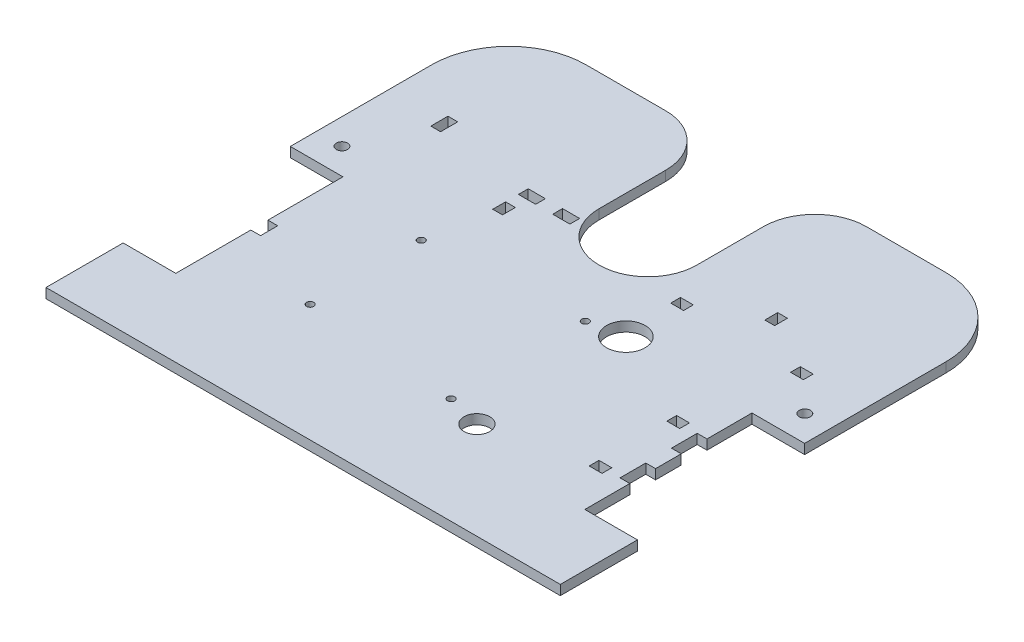
SolidWorks part; units mm, degrees
ref_plane "Front Plane" through (0, 0, 0) normal (0, 0, 1) x (1, 0, 0)
ref_plane "Top Plane" through (0, 0, 0) normal (0, 1, 0) x (1, 0, 0)
ref_plane "Right Plane" through (0, 0, 0) normal (1, 0, 0) x (0, 0, -1)
sketch "Sketch1" plane through (0, 0, 0) normal (0, 1, 0) x (1, 0, 0)
  line L1 (-127, 114.3) -> (127, 114.3)
  line L2 (-127, 114.3) -> (-127, -114.3)
  line L3 (-127, -114.3) -> (127, -114.3)
  line L4 (127, 114.3) -> (127, -114.3)
  line L5 (-127, 114.3) -> (127, -114.3) construction
  line L6 (-127, -114.3) -> (127, 114.3) construction
  point P0 (0, 0)
  dimension "D1" = 254
  dimension "D2" = 228.6
extrude "Boss-Extrude1" add sketch "Sketch1" along normal blind 4.826
sketch "Sketch2" plane through (0, 4.826, 0) normal (0, 1, 0) x (1, 0, 0)
  line L0 (-127, 114.3) -> (-127, -114.3) construction
  line L1 (-127, 6.35) -> (-101, 6.35)
  line L2 (-127, 6.35) -> (-127, -76.2)
  line L3 (-127, -76.2) -> (-101, -76.2)
  line L4 (-101, 6.35) -> (-101, -76.2)
  line L5 (127, -114.3) -> (127, 114.3) construction
  line L6 (127, 6.35) -> (101, 6.35)
  line L7 (127, 6.35) -> (127, -76.2)
  line L8 (127, -76.2) -> (101, -76.2)
  line L9 (101, 6.35) -> (101, -76.2)
  line L10 (-127, -114.3) -> (127, -114.3) construction
  dimension "D1" = 38.1
  dimension "D2" = 38.1
  dimension "D3" = 82.55
  dimension "D4" = 82.55
  dimension "D5" = 26
  dimension "D6" = 26
extrude "Cut-Extrude1" cut sketch "Sketch2" against normal blind 4.826
sketch "Sketch4" plane through (0, 4.826, 0) normal (0, 1, 0) x (1, 0, 0)
  line L0 (0, -114.3) -> (0, 114.3) construction
  line L1 (-127, -114.3) -> (127, -114.3) construction
  line L2 (127, 114.3) -> (-127, 114.3) construction
  line L3 (-127, 76.2) -> (-88.9, 76.2) construction
  line L4 (-127, 114.3) -> (-127, 6.35) construction
  line L5 (-88.9, 76.2) -> (-88.9, 114.3) construction
  line L6 (-127, 76.2) -> (-127, 114.3)
  line L7 (-127, 114.3) -> (-88.9, 114.3)
  line L8 (127, 76.2) -> (127, 114.3)
  line L9 (127, 114.3) -> (88.9, 114.3)
  arc A0 (-127, 76.2) -> (-88.9, 114.3) centre (-88.9, 76.2) cw
  arc A1 (127, 76.2) -> (88.9, 114.3) centre (88.9, 76.2) ccw
  dimension "D1" = 38.1
  dimension "D2" = 38.1
extrude "Cut-Extrude3" cut sketch "Sketch4" against normal blind 4.826
sketch "Sketch17" plane through (0, 0, 0) normal (0, -1, 0) x (1, 0, 0)
  circle A0 centre (114.3, -19.1646) radius 2.7781 construction
  circle A1 centre (-114.3, -19.1646) radius 2.7781 construction
  circle A2 centre (114.3, -19.1646) radius 2.7781
  circle A3 centre (-114.3, -19.1646) radius 2.7781
extrude "Cut-Extrude14" cut sketch "Sketch17" against normal through all
sketch "Sketch18" plane through (0, 4.826, 0) normal (0, 1, 0) x (1, 0, 0)
  line L0 (101, -53.975) -> (96.174, -53.975) construction
  line L1 (96.174, -41.275) -> (96.174, -53.975) construction
  line L2 (101, -41.275) -> (96.174, -41.275) construction
  line L3 (101, -41.275) -> (101, -53.975) construction
  line L4 (101, -15.875) -> (101, -28.575) construction
  line L5 (101, -15.875) -> (96.174, -15.875) construction
  line L6 (96.174, -15.875) -> (96.174, -28.575) construction
  line L7 (101, -28.575) -> (96.174, -28.575) construction
  line L8 (101, -53.975) -> (96.174, -53.975)
  line L9 (96.174, -41.275) -> (96.174, -53.975)
  line L10 (101, -41.275) -> (96.174, -41.275)
  line L11 (101, -41.275) -> (101, -53.975)
  line L12 (101, -15.875) -> (101, -28.575)
  line L13 (101, -15.875) -> (96.174, -15.875)
  line L14 (96.174, -15.875) -> (96.174, -28.575)
  line L15 (101, -28.575) -> (96.174, -28.575)
extrude "Cut-Extrude15" cut sketch "Sketch18" against normal through all
sketch "Sketch19" plane through (0, 4.826, 0) normal (0, 1, 0) x (1, 0, 0)
  line L0 (-101, -39.1583) -> (-101, -30.6917) construction
  line L1 (-101, -39.1583) -> (-96.174, -39.1583) construction
  line L2 (-96.174, -39.1583) -> (-96.174, -30.6917) construction
  line L3 (-101, -30.6917) -> (-96.174, -30.6917) construction
  line L4 (-101, 49.7417) -> (-101, 58.2083) construction
  line L5 (-101, 49.7417) -> (-96.174, 49.7417) construction
  line L6 (-96.174, 49.7417) -> (-96.174, 58.2083) construction
  line L7 (-101, 58.2083) -> (-96.174, 58.2083) construction
  line L8 (-101, -39.1583) -> (-101, -30.6917)
  line L9 (-101, -39.1583) -> (-96.174, -39.1583)
  line L10 (-96.174, -39.1583) -> (-96.174, -30.6917)
  line L11 (-101, -30.6917) -> (-96.174, -30.6917)
  line L12 (-101, 49.7417) -> (-101, 58.2083)
  line L13 (-101, 49.7417) -> (-96.174, 49.7417)
  line L14 (-96.174, 49.7417) -> (-96.174, 58.2083)
  line L15 (-101, 58.2083) -> (-96.174, 58.2083)
extrude "Cut-Extrude16" cut sketch "Sketch19" against normal through all
sketch "Sketch20" plane through (0, 0, 0) normal (0, -1, 0) x (1, 0, 0)
  line L0 (83.474, 51.689) -> (89.824, 51.689) construction
  line L1 (83.474, 56.515) -> (83.474, 51.689) construction
  line L2 (83.474, 56.515) -> (89.824, 56.515) construction
  line L3 (89.824, 56.515) -> (89.824, 51.689) construction
  line L4 (83.474, 13.335) -> (89.824, 13.335) construction
  line L5 (83.474, 18.161) -> (83.474, 13.335) construction
  line L6 (83.474, 18.161) -> (89.824, 18.161) construction
  line L7 (89.824, 18.161) -> (89.824, 13.335) construction
  line L8 (83.474, 51.689) -> (89.824, 51.689)
  line L9 (83.474, 56.515) -> (83.474, 51.689)
  line L10 (83.474, 56.515) -> (89.824, 56.515)
  line L11 (89.824, 56.515) -> (89.824, 51.689)
  line L12 (83.474, 13.335) -> (89.824, 13.335)
  line L13 (83.474, 18.161) -> (83.474, 13.335)
  line L14 (83.474, 18.161) -> (89.824, 18.161)
  line L15 (89.824, 18.161) -> (89.824, 13.335)
extrude "Cut-Extrude17" cut sketch "Sketch20" against normal blind 4.826
sketch "Sketch21" plane through (0, 4.826, 0) normal (0, 1, 0) x (1, 0, 0)
  circle A0 centre (-54.5489, -56.294) radius 1.778 construction
  circle A1 centre (-54.5489, -1.43) radius 1.778 construction
  circle A2 centre (20.6351, -61.882) radius 1.778 construction
  circle A3 centre (20.6351, 4.412) radius 1.778 construction
  circle A4 centre (-54.5489, -56.294) radius 1.778
  circle A5 centre (-54.5489, -1.43) radius 1.778
  circle A6 centre (20.6351, -61.882) radius 1.778
  circle A7 centre (20.6351, 4.412) radius 1.778
extrude "Cut-Extrude18" cut sketch "Sketch21" against normal through all
sketch "Sketch22" plane through (0, 4.826, 0) normal (0, 1, 0) x (1, 0, 0)
  circle A0 centre (37.849, -66.3327) radius 6.35
  circle A1 centre (20.6351, -61.882) radius 1.778 construction
  dimension "D1" = 12.7
  dimension "D2" = 17.78
extrude "Cut-Extrude19" cut sketch "Sketch22" against normal through all
sketch "Sketch24" plane through (0, 0, 0) normal (0, -1, 0) x (1, 0, 0)
  circle A0 centre (0, -55.982) radius 24.13 construction
  circle A1 centre (0, -55.982) radius 24.13
extrude "Cut-Extrude21" cut sketch "Sketch24" against normal through all
sketch "Sketch26" plane through (0, 4.826, 0) normal (0, 1, 0) x (1, 0, 0)
  line L0 (99.476, 38.1) -> (93.126, 38.1) construction
  line L1 (99.476, 38.1) -> (93.126, 38.1)
  line L2 (93.126, 33.274) -> (93.126, 38.1) construction
  line L3 (99.476, 33.274) -> (93.126, 33.274) construction
  line L4 (99.476, 33.274) -> (99.476, 38.1) construction
  line L5 (64.424, 49.276) -> (69.25, 49.276) construction
  line L6 (64.424, 55.626) -> (64.424, 49.276) construction
  line L7 (64.424, 55.626) -> (69.25, 55.626) construction
  line L8 (69.25, 55.626) -> (69.25, 49.276) construction
  line L9 (33.944, 38.1) -> (40.294, 38.1) construction
  line L10 (33.944, 38.1) -> (33.944, 33.274) construction
  line L11 (93.126, 33.274) -> (93.126, 38.1)
  line L12 (99.476, 33.274) -> (93.126, 33.274)
  line L13 (99.476, 33.274) -> (99.476, 38.1)
  line L14 (99.476, 38.1) -> (93.126, 38.1)
  line L15 (64.424, 49.276) -> (69.25, 49.276)
  line L16 (64.424, 55.626) -> (64.424, 49.276)
  line L17 (64.424, 55.626) -> (69.25, 55.626)
  line L18 (69.25, 55.626) -> (69.25, 49.276)
  line L19 (33.944, 38.1) -> (40.294, 38.1)
  line L20 (33.944, 38.1) -> (33.944, 33.274)
  line L21 (33.944, 33.274) -> (40.294, 33.274) construction
  line L22 (40.294, 38.1) -> (40.294, 33.274) construction
  line L23 (33.944, 33.274) -> (40.294, 33.274)
  line L24 (40.294, 38.1) -> (40.294, 33.274)
extrude "Cut-Extrude23" cut sketch "Sketch26" against normal through all contours L18 L17 L16 L15 | L24 L19 L20 L23 | L12 L13 L1 L11 region at (96.301, 4.826, -35.687) region at (66.837, 4.826, -52.451) region at (37.119, 4.826, -35.687)
sketch "Sketch27" plane through (0, 0, 0) normal (0, -1, 0) x (1, 0, 0)
  line L0 (-50.1365, -46.99) -> (-50.1365, -42.164) construction
  line L1 (-50.1365, -46.99) -> (-50.1365, -42.164)
  line L2 (-41.6699, -46.99) -> (-50.1365, -46.99) construction
  line L3 (-41.6699, -46.99) -> (-50.1365, -46.99)
  line L4 (-41.6699, -42.164) -> (-50.1365, -42.164) construction
  line L5 (-41.6699, -42.164) -> (-50.1365, -42.164)
  line L6 (-41.6699, -42.164) -> (-41.6699, -46.99) construction
  line L7 (-24.7365, -46.99) -> (-33.2032, -46.99) construction
  line L8 (-33.2032, -42.164) -> (-33.2032, -46.99) construction
  line L9 (-24.7365, -42.164) -> (-33.2032, -42.164) construction
  line L10 (-24.7365, -46.99) -> (-24.7365, -42.164) construction
  line L11 (-50.1365, -29.464) -> (-50.1365, -35.814) construction
  line L12 (-45.3105, -35.814) -> (-50.1365, -35.814) construction
  line L13 (-45.3105, -29.464) -> (-45.3105, -35.814) construction
  line L14 (-45.3105, -29.464) -> (-50.1365, -29.464) construction
  line L15 (-41.6699, -42.164) -> (-41.6699, -46.99)
  line L16 (-24.7365, -46.99) -> (-33.2032, -46.99)
  line L17 (-33.2032, -42.164) -> (-33.2032, -46.99)
  line L18 (-24.7365, -42.164) -> (-33.2032, -42.164)
  line L19 (-24.7365, -46.99) -> (-24.7365, -42.164)
  line L20 (-50.1365, -29.464) -> (-50.1365, -35.814)
  line L21 (-45.3105, -35.814) -> (-50.1365, -35.814)
  line L22 (-45.3105, -29.464) -> (-45.3105, -35.814)
  line L23 (-45.3105, -29.464) -> (-50.1365, -29.464)
extrude "Cut-Extrude24" cut sketch "Sketch27" against normal through all
sketch "Sketch28" plane through (0, 4.826, 0) normal (0, 1, 0) x (1, 0, 0)
  line L0 (-24.13, 55.982) -> (-24.13, 114.3)
  line L1 (88.9, 114.3) -> (-88.9, 114.3) construction
  line L2 (24.13, 55.982) -> (24.13, 114.3)
  line L3 (24.13, 114.3) -> (-24.13, 114.3)
  circle A0 centre (0, 55.982) radius 24.13 construction
  circle A1 centre (0, 55.982) radius 24.13
extrude "Cut-Extrude25" cut sketch "Sketch28" against normal through all contours A1 L2 L3 L0 region at (0, 4.826, -94.2484)
fillet "Fillet1" radius 25.4 2 edges at (-24.13, 2.413, -114.3) (24.13, 2.413, -114.3)
sketch "Sketch29" plane through (0, 4.826, 0) normal (0, 1, 0) x (1, 0, 0)
  line L0 (33.944, 33.274) -> (40.294, 33.274) construction
  circle A0 centre (37.2178, 7.874) radius 9.525
  dimension "D1" = 19.05
  dimension "D2" = 25.4
extrude "Cut-Extrude26" cut sketch "Sketch29" against normal through all
equation "\"MDF\"= 0.19in"
equation "\"GenDiameter\"= 60mm"
equation "\"GenCutDiameter\" = 1.8in"
equation "\"GenCutDistance\" = 1"
equation "\"TowerHeight\" = 6in"
equation "\"TowerFrontBase\" = 3in"
equation "\"FunnelHeight\" = 1in"
equation "\"FunnelAngle\" = 20"
equation "\"TowerSideBase\" = 3in"
equation "\"BaseLength\" = 9in"
equation "\"BaseWidth\" = 10in"
equation "\"WheelHoleLength\" = 3.25in"
equation "\"WheelHoleWidth\" = 26mm"
equation "\"DropLength\" = 1in"
equation "\"D1@Sketch1\"=\"BaseWidth\""
equation "\"D2@Sketch1\"=\"BaseLength\""
equation "\"D1@Boss-Extrude1\"=\"MDF\""
equation "\"WheelHoleFromBack\" = 1.5in"
equation "\"D1@Sketch2\"=\"WheelHoleFromBack\""
equation "\"D2@Sketch2\"=\"WheelHoleFromBack\""
equation "\"D3@Sketch2\"=\"WheelHoleLength\""
equation "\"D4@Sketch2\"=\"WheelHoleLength\""
equation "\"D5@Sketch2\"=\"WheelHoleWidth\""
equation "\"D6@Sketch2\"=\"WheelHoleWidth\""
equation "\"D1@Cut-Extrude1\"=\"MDF\""
equation "\"DropWidth\" = 8.5in"
equation "\"BumperWidth\" = 2in"
equation "\"D1@Cut-Extrude3\"=\"MDF\""
equation "\"DropWidthTop\" = 0in"
equation "\"D1@Cut-Extrude17\"=\"MDF\""
